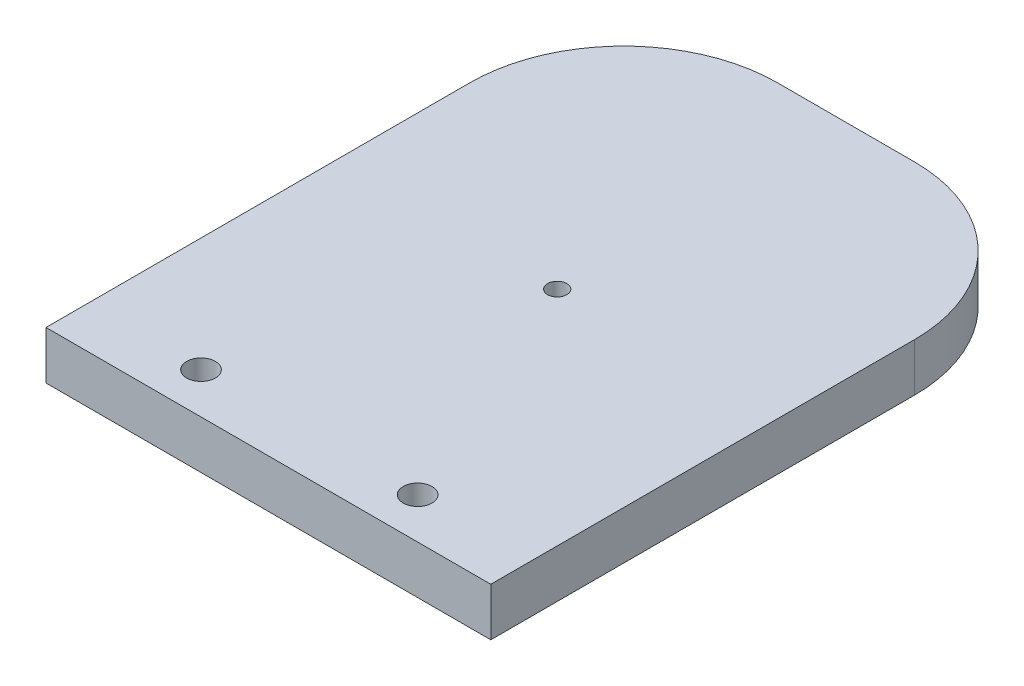
SolidWorks part; units mm, degrees
ref_plane "Front" through (0, 0, 0) normal (0, 0, 1) x (1, 0, 0)
ref_plane "Top" through (0, 0, 0) normal (0, 1, 0) x (1, 0, 0)
ref_plane "Right" through (0, 0, 0) normal (1, 0, 0) x (0, 0, -1)
sketch "Sketch1" plane through (0, 0, 0) normal (0, 1, 0) x (1, 0, 0)
  line L0 (0, 0) -> (0, 76.2)
  line L1 (0, 0) -> (58.674, 0)
  line L2 (0, 76.2) -> (58.674, 76.2)
  line L3 (58.674, 0) -> (58.674, 76.2)
  dimension "D1" = 58.674
  dimension "D2" = 76.2
  dimension "D3" = 90
extrude "Boss-Extrude1" add sketch "Sketch1" along normal blind 6.35
sketch "Sketch2" plane through (0, 6.35, 0) normal (0, 1, 0) x (1, 0, 0)
  line L0 (0, 0.2226) -> (0, 38.1)
  line L3 (0, 38.1) -> (58.674, 38.1)
  line L4 (58.674, 0) -> (58.674, 76.2) construction
  line L6 (0, 76.2) -> (0, 0) construction
  circle A0 centre (29.337, 38.1) radius 1.27
  dimension "D1" = 2.54
extrude "Cut-Extrude1" cut sketch "Sketch2" against normal through all contours L3 A0 | L3 A0 region at (29.337, 6.35, -38.639) region at (29.337, 6.35, -37.561)
sketch "Sketch3" plane through (0, 0, 0) normal (0, 0, 1) x (1, 0, 0)
  line L1 (0, 6.35) -> (58.674, 6.35)
  line L2 (0, 6.35) -> (0, 0)
  line L3 (0, 0) -> (58.674, 0)
  line L4 (58.674, 6.35) -> (58.674, 0)
extrude "Boss-Extrude2" add sketch "Sketch3" along normal blind 7.62
sketch "Sketch4" plane through (0, 6.35, 0) normal (0, 1, 0) x (1, 0, 0)
  line L0 (0, 0) -> (58.674, 0)
  line L1 (58.674, 0) -> (58.674, -7.62)
  line L2 (58.674, -7.62) -> (0, -7.62)
  line L3 (0, -7.62) -> (0, 0)
  line L4 (15.24, 0) -> (15.24, -7.62)
  line L5 (21.717, 0) -> (21.717, -7.62)
  line L6 (36.957, 0) -> (36.957, -7.62)
  line L7 (43.434, 0) -> (43.434, -7.62)
  line L8 (0, -2.7708) -> (15.24, -2.7708) construction
  line L9 (15.24, -2.7708) -> (21.717, -2.7708) construction
  line L10 (21.717, -2.7708) -> (36.957, -2.7708) construction
  line L11 (36.957, -2.7708) -> (43.434, -2.7708) construction
  line L12 (43.434, -2.7708) -> (58.674, -2.7708) construction
  line M3 (0, 76.2) -> (0, -7.62)
  line M4 (0, -7.62) -> (58.674, -7.62)
  line M5 (58.674, -7.62) -> (58.674, 76.2)
  dimension "D1" = 15.24
extrude "Cut-Extrude2" cut sketch "Sketch4" against normal through all contours L4 L0 M3 M4 | L6 L0 L5 M4 | L0 L7 M4 M5 region at (7.62, 6.35, 3.81) region at (29.337, 6.35, 3.81) region at (51.054, 6.35, 3.81)
fillet "Fillet1" radius 3.175 4 edges at (40.1955, 0, 7.62) (40.1955, 6.35, 7.62) (18.4785, 0, 7.62) (18.4785, 6.35, 7.62)
sketch "Sketch5" plane through (43.434, 0, 0) normal (1, 0, 0) x (0, 0, -1)
  line L0 (-4.445, 6.35) -> (-4.445, 0) construction
  circle A0 centre (-4.445, 3.175) radius 2.54
  dimension "D1" = 5.08
extrude "Cut-Extrude3" cut sketch "Sketch5" against normal through all
fillet "Fillet2" radius 20.32 2 edges at (58.674, 3.175, -76.2) (0, 3.175, -76.2)
sketch "Sketch7" plane through (0, 6.35, 0) normal (0, 1, 0) x (1, 0, 0)
  line L1 (0, 0) -> (58.9278, 0)
  line L2 (0, 0) -> (0, -8.2417)
  line L3 (0, -8.2417) -> (58.9278, -8.2417)
  line L4 (58.9278, 0) -> (58.9278, -8.2417)
extrude "Cut-Extrude4" cut sketch "Sketch7" against normal through all
sketch "Sketch8" plane through (0, 6.35, 0) normal (0, 1, 0) x (1, 0, 0)
  circle A0 centre (43.6245, 5.3975) radius 1.8986
  circle A1 centre (15.0495, 5.3975) radius 1.8987
extrude "Cut-Extrude5" cut sketch "Sketch8" against normal through all
